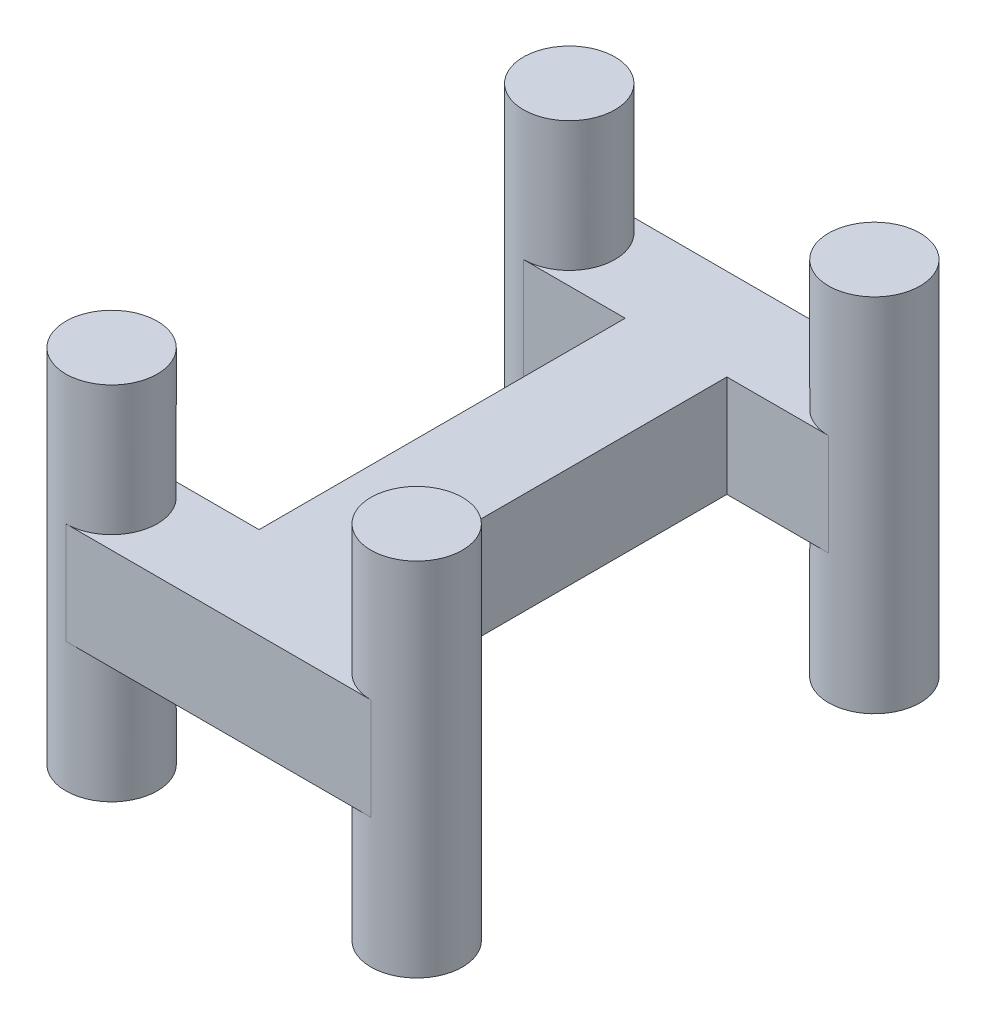
SolidWorks part; units mm, degrees
ref_plane "Front Plane" through (0, 0, 0) normal (0, 0, 1) x (1, 0, 0)
ref_plane "Top Plane" through (0, 0, 0) normal (0, 1, 0) x (1, 0, 0)
ref_plane "Right Plane" through (0, 0, 0) normal (1, 0, 0) x (0, 0, -1)
sketch "Sketch1" plane through (0, 0, 0) normal (0, 1, 0) x (1, 0, 0)
  line L0 (0, -10.8) -> (0, 10.8) construction
  line L1 (-6, -9) -> (6, -9) construction
  line L2 (-6, -9) -> (-6, 9) construction
  line L3 (-6, 9) -> (6, 9) construction
  line L4 (6, -9) -> (6, 9) construction
  line L5 (-6, -9) -> (6, 9) construction
  line L6 (-6, 9) -> (6, -9) construction
  line L7 (-6, -10.8) -> (6, -10.8)
  line L8 (6, -7.2) -> (2, -7.2)
  line L9 (-2, 7.2) -> (-2, -7.2)
  line L10 (-6, 7.2) -> (-2, 7.2)
  line L12 (6, 10.8) -> (-6, 10.8)
  line L13 (2, -7.2) -> (2, 7.2)
  line L14 (2, 7.2) -> (6, 7.2)
  line L15 (-2, -7.2) -> (-6, -7.2)
  circle A0 centre (-6, 9) radius 1.8
  circle A1 centre (6, 9) radius 1.8
  circle A2 centre (6, -9) radius 1.8
  circle A3 centre (-6, -9) radius 1.8
  point P0 (0, 0)
  point P24 (0, 0)
  dimension "D3" = 3.6
  dimension "D4" = 3.6
  dimension "D5" = 3.6
  dimension "D6" = 3.6
  dimension "D1" = 18
  dimension "D2" = 12
  dimension "D7" = 2
  dimension "D8" = 2
extrude "Boss-Extrude1" add sketch "Sketch1" along normal blind 2 and the other way blind 2 contours A3 L7 A2 L8 L13 L14 A1 L12 A0 L10 L9 L15 region at (0, 0, 0)
extrude "Boss-Extrude2" add sketch "Sketch1<4>" along normal blind 7.1 and the other way blind 7.1 contours A0 | A1 | A3 | A2 region at (-6, 0, 9) region at (6, 0, 9) region at (-6, 0, -9) region at (6, 0, -9)
sketch "Sketch1<4>" plane through (0, 0, 0) normal (0, 1, 0) x (1, 0, 0) same geometry as "Sketch1"
equation "\"2.5.00mm\"=10"
